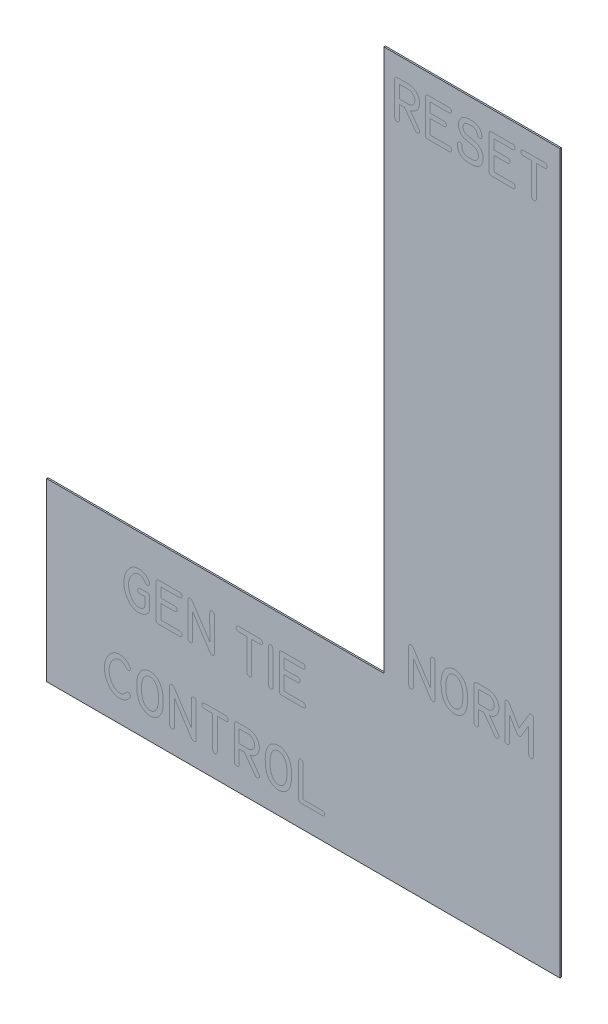
SolidWorks part; units mm, degrees
ref_plane "Front Plane" through (0, 0, 0) normal (0, 0, 1) x (1, 0, 0)
ref_plane "Top Plane" through (0, 0, 0) normal (0, 1, 0) x (1, 0, 0)
ref_plane "Right Plane" through (0, 0, 0) normal (1, 0, 0) x (0, 0, -1)
sketch "Sketch1" plane through (0, 0, 0) normal (0, 0, 1) x (1, 0, 0)
  line L6 (0, 50.8) -> (0, 113.03)
  line L7 (0, 113.03) -> (-15.24, 113.03)
  line L8 (-15.24, 113.03) -> (-15.24, 66.04)
  line L9 (-15.24, 66.04) -> (-44.45, 66.04)
  line L10 (-44.45, 66.04) -> (-44.45, 50.8)
  line L11 (-44.45, 50.8) -> (0, 50.8)
  line L12 (0, 50.8) -> (0, 113.03)
  line L13 (0, 113.03) -> (-15.24, 113.03)
  line L14 (-15.24, 113.03) -> (-15.24, 66.04)
  line L15 (-15.24, 66.04) -> (-44.45, 66.04)
  line L16 (-44.45, 66.04) -> (-44.45, 50.8)
  line L17 (-44.45, 50.8) -> (0, 50.8)
  dimension "D1" = 0
extrude "Boss-Extrude1" add sketch "Sketch1" along normal blind 0.127
sketch "Sketch2" plane through (0, 0, 0.127) normal (0, 0, 1) x (1, 0, 0)
  line L0 (-15.24, 107.9999) -> (0, 107.9999) construction
  line L1 (-15.24, 113.03) -> (-15.24, 66.04) construction
  line L2 (0, 50.8) -> (0, 113.03) construction
  line L3 (-15.24, 66.04) -> (0, 66.04) construction
  line L4 (-15.24, 66.04) -> (-15.24, 50.8) construction
  line L5 (-44.45, 50.8) -> (0, 50.8) construction
  line L6 (-15.24, 59.9598) -> (-44.45, 59.9598) construction
  line L7 (-44.45, 66.04) -> (-44.45, 50.8) construction
  line L8 (-15.24, 52.7037) -> (-44.45, 52.7037) construction
  text T0 "RESET"
  text T1 "NORM"
  text T2 "GEN TIE"
  text T3 "CONTROL"
wrap "Wrap1" sketch "Sketch2" wrap type scribe source sketch "Sketch2" face at (-19.8967, 76.6233, 0.127)
